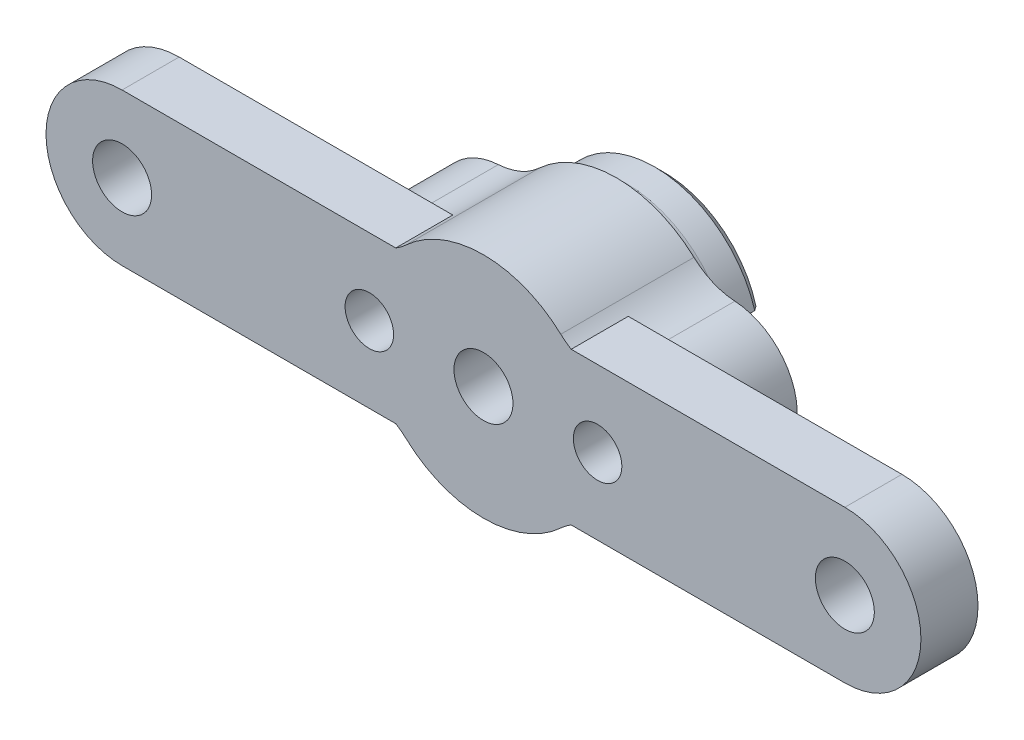
SolidWorks part; units mm, degrees
ref_plane "前视基准面" through (0, 0, 0) normal (0, 0, 1) x (1, 0, 0)
ref_plane "上视基准面" through (0, 0, 0) normal (0, 1, 0) x (1, 0, 0)
ref_plane "右视基准面" through (0, 0, 0) normal (1, 0, 0) x (0, 0, -1)
sketch "草图1" plane through (0, 0, 0) normal (0, 0, 1) x (1, 0, 0)
  line L0 (4.4721, 4) -> (19, 4)
  line L1 (-19, -4) -> (-4.4721, -4)
  line L2 (4.4721, -4) -> (19, -4)
  line L3 (-19, 4) -> (-4.4721, 4)
  circle A0 centre (0, 0) radius 1.55
  circle A1 centre (19, 0) radius 1.55
  circle A2 centre (-19, 0) radius 1.55
  arc A3 (-19, 4) -> (-19, -4) centre (-19, 0) ccw
  arc A4 (19, -4) -> (19, 4) centre (19, 0) ccw
  arc A5 (-4.4721, -4) -> (4.4721, -4) centre (0, 0) ccw
  arc A6 (4.4721, 4) -> (-4.4721, 4) centre (0, 0) ccw
  circle A7 centre (-6, 0) radius 1.275
  circle A8 centre (6, 0) radius 1.275
  dimension "D3" = 3.1
  dimension "D4" = 3.1
  dimension "D5" = 3.1
  dimension "D8" = 12
  dimension "D7" = 8
  dimension "D9" = 4
  dimension "D6" = 8
  dimension "D11" = 2.55
  dimension "D12" = 2.55
  dimension "D1" = 19
  dimension "D2" = 19
  dimension "D10" = 4
  dimension "D13" = 6
  dimension "D14" = 6
extrude "凸台-拉伸1" add sketch "草图1" along normal blind 3
sketch "草图2" plane through (0, 0, 0) normal (0, 0, -1) x (-1, 0, 0)
  arc A1 (-4.9792, 3.3478) -> (-4.9792, -3.3478) centre (-6, 0) ccw
  circle A2 centre (-6, 0) radius 1.275
  circle A3 centre (6, 0) radius 1.275
  arc A4 (-4.9792, -3.3478) -> (4.9792, -3.3478) centre (0, 0) ccw
  arc A5 (4.9792, -3.3478) -> (4.9792, 3.3478) centre (6, 0) ccw
  arc A7 (4.9792, 3.3478) -> (-4.9792, 3.3478) centre (0, 0) ccw
  dimension "D1" = 2.55
  dimension "D2" = 6
  dimension "D3" = 2.55
  dimension "D6" = 7
  dimension "D7" = 7
extrude "凸台-拉伸2" add sketch "草图2" along normal blind 4
fillet "圆角1" radius 3.5 4 edges at (4.9792, 3.3478, -2) (-4.9792, 3.3478, -2) (-4.9792, -3.3478, -2) (4.9792, -3.3478, -2)
sketch "草图3" plane through (0, 0, -4) normal (0, 0, -1) x (-1, 0, 0)
  circle A0 centre (0, 0) radius 5.5
  dimension "D1" = 11
extrude "凸台-拉伸3" add sketch "草图3" along normal blind 2.5
sketch "草图4" plane through (0, 0, -4) normal (0, 0, -1) x (-1, 0, 0)
  circle A0 centre (-6, 0) radius 1.75
  circle A1 centre (6, 0) radius 1.75
  dimension "D1" = 3.5
  dimension "D2" = 3.5
sketch "草图5" plane through (0, 0, -6.5) normal (0, 0, -1) x (-1, 0, 0)
  circle A0 centre (0, 0) radius 2.6
  dimension "D1" = 5.2
sketch "草图7" plane through (0, 0, -6.5) normal (0, 0, -1) x (-1, 0, 0)
  circle A0 centre (0, 2.6) radius 0.35
  circle A1 centre (0, 0) radius 2.6 construction
  dimension "D1" = 0.7
extrude "切除-拉伸4" cut sketch "草图7" against normal blind 3.5 contours A0
pattern_circular "阵列(圆周)1" count 25 over 360 about axis through (0, 0, -6.5) along (0, 0, -1) of "切除-拉伸4"
extrude "切除-拉伸6" cut sketch "草图5" against normal blind 3.5
extrude "切除-拉伸7" cut sketch "草图4" against normal mid plane 8
sketch "草图8" plane through (0, 0, -3) normal (0, 0, -1) x (-1, 0, 0)
  circle A0 centre (0, 0) radius 1.55
  dimension "D1" = 3.1
extrude "切除-拉伸8" cut sketch "草图8" against normal blind 6
fillet "圆角2" radius 0.5 2 edges at (0, 5.5, -4) (0, -5.5, -4)
chamfer "倒角1" distance 0.5 angle 45 2 edges at (0, -5.5, -6.5) (0, 5.5, -6.5)
